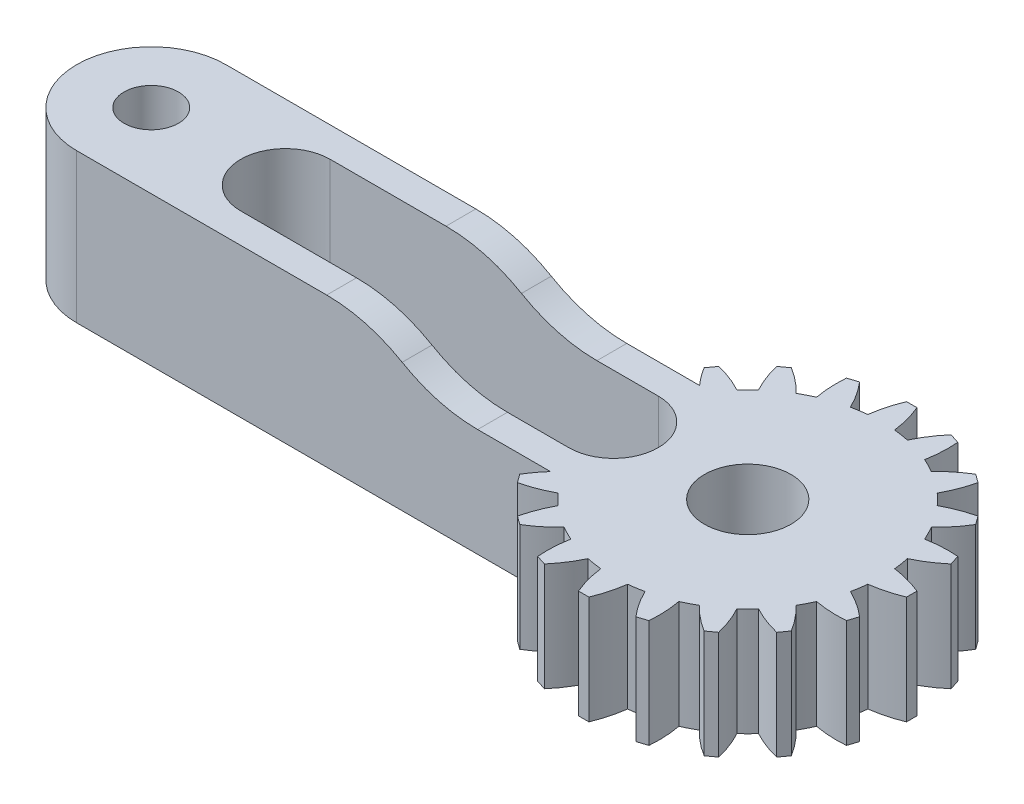
SolidWorks part; units mm, degrees
material "ABS"
ref_plane "Ebene vorne" through (0, 0, 0) normal (0, 0, 1) x (1, 0, 0)
ref_plane "Ebene oben" through (0, 0, 0) normal (0, 1, 0) x (1, 0, 0)
ref_plane "Ebene rechts" through (0, 0, 0) normal (1, 0, 0) x (0, 0, -1)
sketch "Skizze2" plane through (0, 0, 0) normal (0, 1, 0) x (1, 0, 0)
  line L0 (-20, 5) -> (20, 5)
  line L1 (0, 0) -> (0, 16.3031) construction
  line L2 (0, 0) -> (-44.1058, 0) construction
  line L3 (-20, -5) -> (20, -5)
  arc A0 (-20, -5) -> (-20, 5) centre (-20, 0) cw
  arc A1 (20, -5) -> (20, 5) centre (20, 0) ccw
  circle A2 centre (-20, 0) radius 1.825
  circle A3 centre (20, 0) radius 2.9
  point P4 (0, 5)
  point P12 (0, -5)
  dimension "D3" = 3.65
  dimension "D4" = 5.8
  dimension "D1" = 5
  dimension "D2" = 40
extrude "Aufsatz-Linear austragen1" add sketch "Skizze2" along normal blind 10
sketch "Skizze4" plane through (0, 10, 0) normal (0, 1, 0) x (1, 0, 0)
  line L0 (20, 5) -> (0, 5)
  line L1 (20, 5) -> (-20, 5) construction
  line L2 (0, 5) -> (0, -5)
  line L3 (-20, -5) -> (20, -5) construction
  line L4 (0, -5) -> (20, -5)
  arc A0 (20, 5) -> (20, -5) centre (20, 0) cw
  arc A1 (20, -5) -> (20, 5) centre (20, 0) ccw construction
extrude "Schnitt-Linear austragen1" cut sketch "Skizze4" against normal blind 2.75
fillet "Verrundung1" radius 10 1 edges at (0, 7.25, 0)
fillet "Verrundung2" radius 10 1 edges at (0, 10, 0)
sketch "Skizze5" plane through (0, 7.25, 0) normal (0, 1, 0) x (1, 0, 0)
  circle A0 centre (20, 0) radius 5
  arc A1 (20, -5) -> (20, 5) centre (20, 0) ccw construction
  circle A2 centre (20, 0) radius 9
  dimension "D1" = 18
extrude "Aufsatz-Linear austragen2" add sketch "Skizze5" against normal up to surface (7.25 mm away) up to face at (20, 0, 2.9)
sketch "Skizze6" plane through (0, 7.25, 0) normal (0, 1, 0) x (1, 0, 0)
  line L0 (20, 0) -> (35.1018, 0) construction
  line L1 (31, -0.35) -> (31, 0.35)
  arc A0 (28.9549, -0.9) -> (31, -0.35) centre (27.9268, 7) ccw
  circle A2 centre (20, 0) radius 2.9 construction
  arc A3 (28.9549, 0.9) -> (28.9549, -0.9) centre (20, 0) cw
  arc A4 (12.5167, -5) -> (12.5167, 5) centre (20, 0) ccw construction
  arc A5 (28.9549, 0.9) -> (31, 0.35) centre (27.9268, -7) cw
  point P6 (31, 0)
  point P10 (29, 0)
  point P14 (30.8155, 0.3553)
  dimension "D1" = 2
  dimension "D2" = 1.8
  dimension "D3" = 0.7
  dimension "D4" = 7
extrude "Aufsatz-Linear austragen3" add sketch "Skizze6" against normal up to surface (7.25 mm away) up to face at (-0.8708, 0, 0)
pattern_circular "Kreismuster1" count 20 over 360 about axis through (20, 7.25, 0) along (0, 1, 0) of "Aufsatz-Linear austragen3"
sketch "Skizze7" plane through (0, 0, -5) normal (0, 0, -1) x (-1, 0, 0)
  line L0 (-8.4507, 2.7562) -> (17.6204, 2.7562) construction
  text T0 "6-DOFRA" font "Century Gothic" height 4
extrude "Schnitt-Linear austragen2" [suppressed] cut sketch "Skizze7" against normal blind 0.25
sketch "Skizze9" plane through (0, 0, 0) normal (0, -1, 0) x (1, 0, 0)
  line L0 (-11, 0) -> (11, 0) construction
  line L1 (-11, 3) -> (11, 3)
  line L2 (-11, -3) -> (11, -3)
  arc A0 (-11, 3) -> (-11, -3) centre (-11, 0) ccw
  arc A1 (11, -3) -> (11, 3) centre (11, 0) ccw
  point P3 (0, 0)
  dimension "D1" = 6
  dimension "D2" = 22
extrude "Schnitt-Linear austragen3" cut sketch "Skizze9" against normal through all
